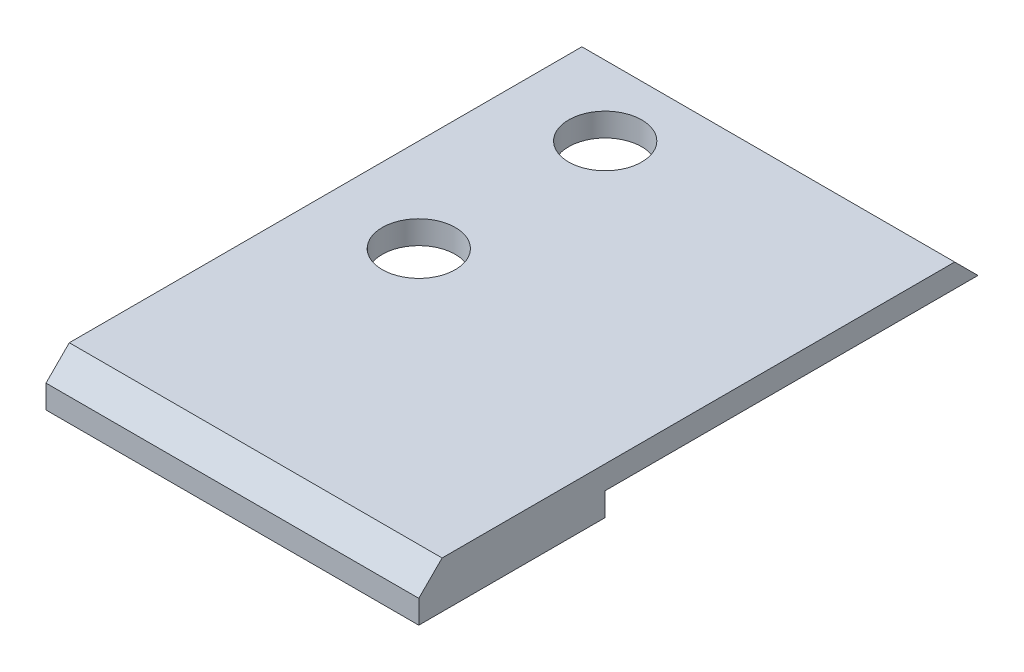
SolidWorks part; units mm, degrees
ref_plane "Front Plane" through (0, 0, 0) normal (0, 0, 1) x (1, 0, 0)
ref_plane "Top Plane" through (0, 0, 0) normal (0, 1, 0) x (1, 0, 0)
ref_plane "Right Plane" through (0, 0, 0) normal (1, 0, 0) x (0, 0, -1)
sketch "Sketch1" plane through (0, 0, 0) normal (0, 1, 0) x (1, 0, 0)
  line L0 (0, 12.7) -> (25.4, 12.7)
  line L1 (0, 0) -> (25.4, 0)
  line L2 (0, 0) -> (0, 38.1)
  line L3 (0, 38.1) -> (25.4, 38.1)
  line L4 (25.4, 0) -> (25.4, 38.1)
  circle A0 centre (6.35, 19.05) radius 2.4892
  circle A1 centre (6.35, 31.75) radius 2.4892
  dimension "D3" = 4.9784
  dimension "D1" = 38.1
  dimension "D2" = 25.4
  dimension "D4" = 6.35
  dimension "D5" = 19.05
  dimension "D6" = 25.4
  dimension "D7" = 6.35
  dimension "D8" = 6.35
extrude "Boss-Extrude1" add sketch "Sketch1" against normal blind 1.5875 contours L0 L4 L3 L2 A1 A0 region at (13.1078, 0, -25.4)
extrude "Boss-Extrude2" add sketch "Sketch1<3>" against normal blind 3.175 contours L1 L4 L0 L2 region at (12.7, 0, -6.35)
sketch "Sketch1<3>" plane through (0, 0, 0) normal (0, 1, 0) x (1, 0, 0) same geometry as "Sketch1"
chamfer "Chamfer1" distance 1.5875 angle 45 2 edges at (12.7, 0, -38.1) (12.7, 0, 0)
